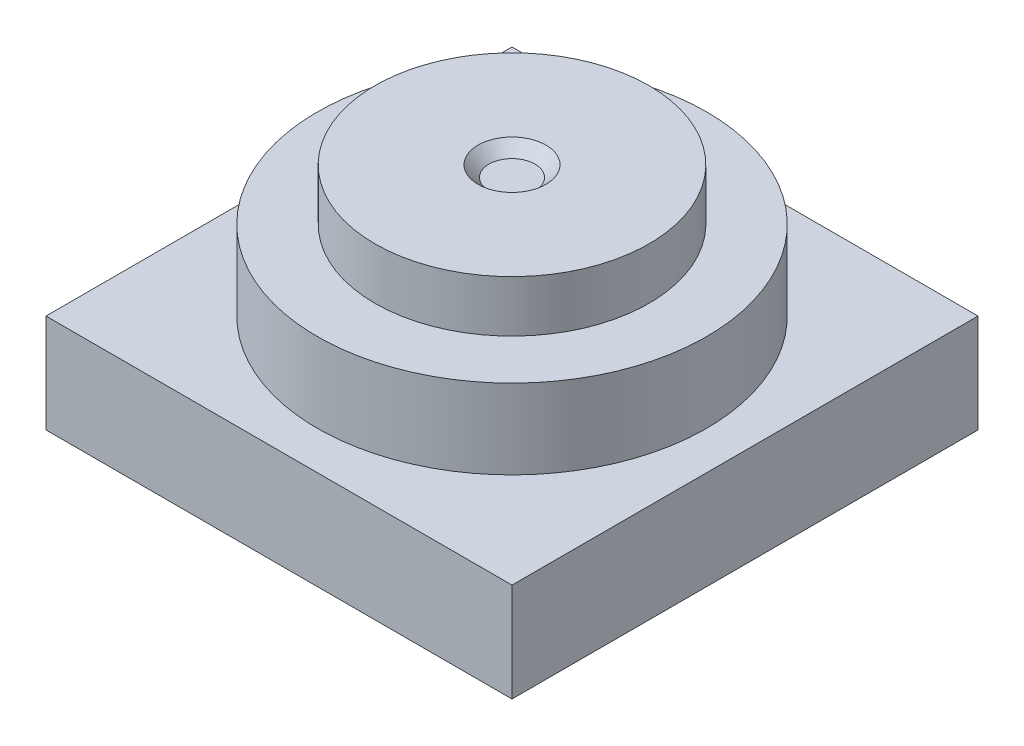
SolidWorks part; units mm, degrees
ref_plane "前视基准面" through (0, 0, 0) normal (0, 0, 1) x (1, 0, 0)
ref_plane "上视基准面" through (0, 0, 0) normal (0, 1, 0) x (1, 0, 0)
ref_plane "右视基准面" through (0, 0, 0) normal (1, 0, 0) x (0, 0, -1)
sketch "草图1" plane through (0, 0, 0) normal (0, 1, 0) x (1, 0, 0)
  line L1 (-4.25, 4.25) -> (4.25, 4.25)
  line L2 (-4.25, 4.25) -> (-4.25, -4.25)
  line L3 (-4.25, -4.25) -> (4.25, -4.25)
  line L4 (4.25, 4.25) -> (4.25, -4.25)
  line L5 (-4.25, 4.25) -> (4.25, -4.25) construction
  line L6 (-4.25, -4.25) -> (4.25, 4.25) construction
  circle A0 centre (0, 0) radius 3.55
  circle A1 centre (0, 0) radius 2.5
  point P0 (0, 0)
  dimension "D2" = 7.1
  dimension "D3" = 5
  dimension "D1" = 8.5
extrude "凸台-拉伸2" add sketch "草图1" along normal blind 1.8 contours L4 L1 L2 L3 A0 region at (0, 0, -4.1298)
extrude "凸台-拉伸3" add sketch "草图1<3>" along normal blind 3.25 contours A0 A1 region at (-3.4496, 0, 0)
sketch "草图1<3>" plane through (0, 0, 0) normal (0, 1, 0) x (1, 0, 0) same geometry as "草图1"
extrude "凸台-拉伸4" add sketch "草图1<4>" along normal blind 4.19 contours A1 region at (0, 0, 0)
sketch "草图1<4>" plane through (0, 0, 0) normal (0, 1, 0) x (1, 0, 0) same geometry as "草图1"
sketch "草图3" plane through (0, 4.19, 0) normal (0, 1, 0) x (1, 0, 0)
  circle A0 centre (0, 0) radius 0.42
  dimension "D1" = 0.84
extrude "切除-拉伸1" cut sketch "草图3" against normal blind 0.2
chamfer "倒角1" distance 0.2 angle 45 1 edges at (0, 4.19, 0.42)
